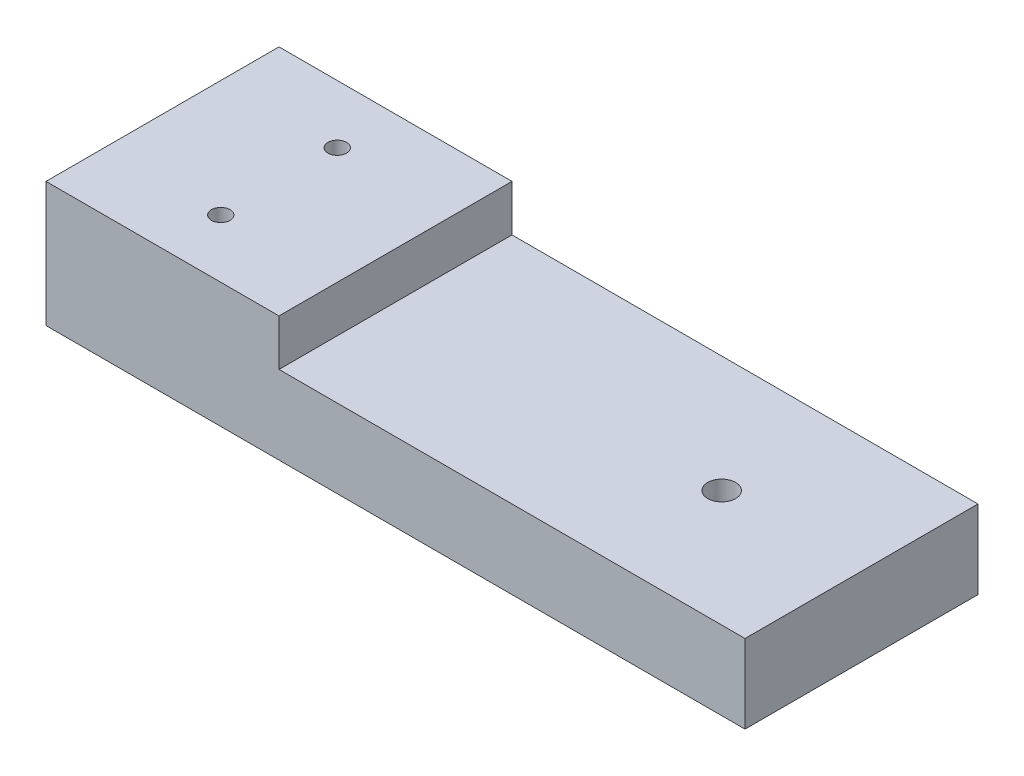
SolidWorks part; units mm, degrees
material "Balsa"
ref_plane "Front Plane" through (0, 0, 0) normal (0, 0, 1) x (1, 0, 0)
ref_plane "Top Plane" through (0, 0, 0) normal (0, 1, 0) x (1, 0, 0)
ref_plane "Right Plane" through (0, 0, 0) normal (1, 0, 0) x (0, 0, -1)
sketch "Sketch1" plane through (0, 0, 0) normal (0, 1, 0) x (1, 0, 0)
  line L1 (0, 0) -> (50, 0)
  line L2 (0, 0) -> (0, 50)
  line L3 (0, 50) -> (50, 50)
  line L4 (50, 0) -> (50, 50)
  line L5 (0, 0) -> (50, 50) construction
  line L6 (0, 50) -> (50, 0) construction
  line L7 (0, 50) -> (150, 50)
  line L8 (0, 50) -> (0, 0)
  line L9 (0, 0) -> (150, 0)
  line L10 (150, 50) -> (150, 0)
  line L11 (0, 50) -> (150, 0) construction
  line L12 (0, 0) -> (150, 50) construction
  point P4 (25, 25)
  point P8 (75, 25)
  dimension "D1" = 50
  dimension "D3" = 100
  dimension "D4" = 50
extrude "Boss-Extrude1" add sketch "Sketch1" along normal blind 26.8 contours L1 L4 L3 L2 region at (25, 0, -25)
extrude "Boss-Extrude2" add sketch "Sketch1<3>" along normal blind 16.85 contours L10 L7 L4 L9 region at (100, 0, -25)
sketch "Sketch1<3>" plane through (0, 0, 0) normal (0, 1, 0) x (1, 0, 0) same geometry as "Sketch1"
sketch "Sketch2" plane through (0, 0, 0) normal (0, -1, 0) x (1, 0, 0)
  line L0 (0, 0) -> (50, 0) construction
  line L1 (0, 0) -> (150, 0) construction
  line L2 (25, 0) -> (25, -50)
  line L3 (0, -50) -> (150, -50) construction
  line L4 (25, -25) -> (150, -25)
  line L5 (150, -50) -> (150, 0) construction
  circle A0 centre (25, -37.5) radius 2
  circle A1 centre (25, -12.5) radius 2
  circle A2 centre (120, -25) radius 3
  point P5 (25, 0)
  dimension "D2" = 25
  dimension "D3" = 12.5
  dimension "D4" = 4
  dimension "D5" = 4
  dimension "D6" = 6
  dimension "D7" = 30
  dimension "D1" = 50
  dimension "D8" = 25
extrude "Cut-Extrude1" cut sketch "Sketch2" against normal through all contours A1 | A0 | A2
